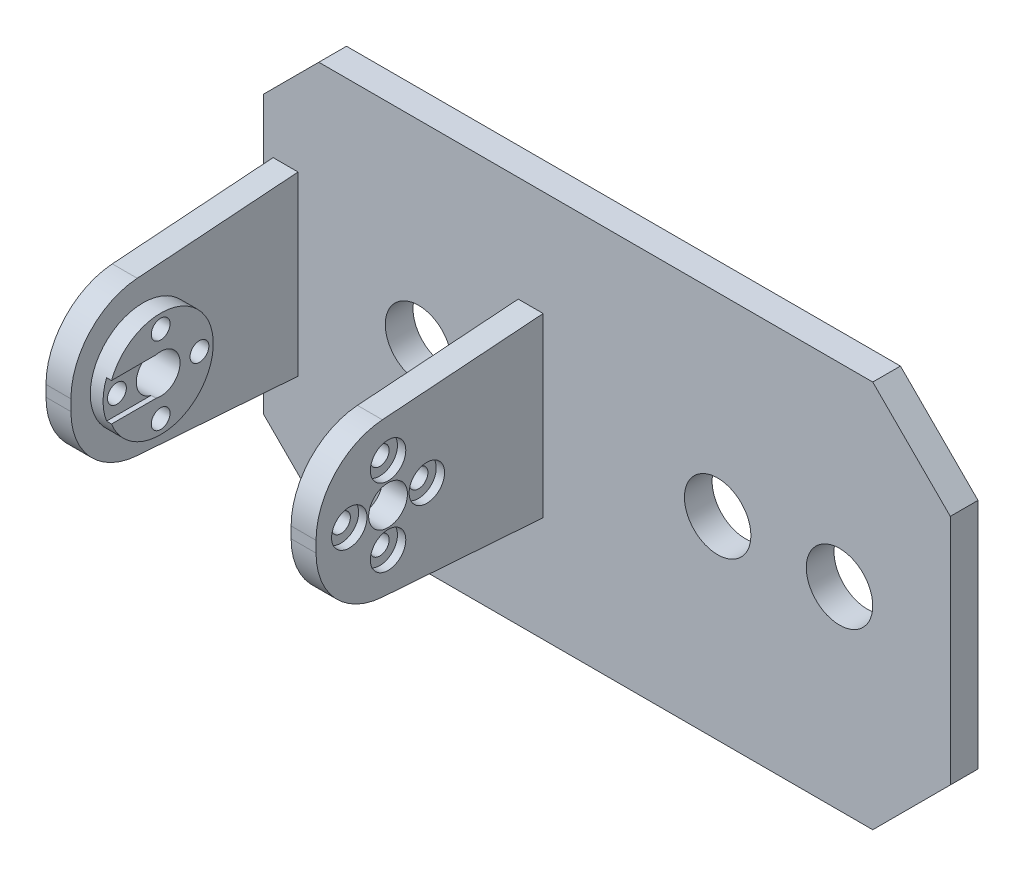
SolidWorks part; units mm, degrees
ref_plane "Front Plane" through (0, 0, 0) normal (0, 0, 1) x (1, 0, 0)
ref_plane "Top Plane" through (0, 0, 0) normal (0, 1, 0) x (1, 0, 0)
ref_plane "Right Plane" through (0, 0, 0) normal (1, 0, 0) x (0, 0, -1)
ref_plane "PZ_m33_000" through (0, 0, -33) normal (0, 0, 1) x (1, 0, 0)
sketch "S_prism1" plane through (0, 0, -33) normal (0, 0, 1) x (1, 0, 0)
  line L0 (56, -21) -> (56, 21)
  line L1 (56, 21) -> (42, 35)
  line L2 (42, 35) -> (-58, 35)
  line L3 (-58, 35) -> (-68, 25)
  line L4 (-68, 25) -> (-68, -25)
  line L5 (-68, -25) -> (-58, -35)
  line L6 (-58, -35) -> (42, -35)
  line L7 (42, -35) -> (56, -21)
extrude "Boss_1" add sketch "S_prism1" along normal blind 5
ref_plane "PX_m22_000" through (-22, 0, 0) normal (1, 0, 0) x (0, 0, -1)
sketch "S_prism2" plane through (-22, 0, 0) normal (1, 0, 0) x (0, 0, -1)
  line L0 (28.5, -16) -> (28.5, 16)
  line L1 (28.5, 16) -> (-1.0301, 13.8653)
  line L2 (-13, 0.9989) -> (-13, -0.9989)
  line L3 (-1.0301, -13.8653) -> (28.5, -16)
  arc A0 (-1.0301, 13.8653) -> (-13, 0.9989) centre (-0.1001, 0.999) ccw
  arc A1 (-13, -0.9989) -> (-1.0301, -13.8653) centre (-0.1001, -0.999) ccw
extrude "Boss_2" add sketch "S_prism2" along normal blind 4.5
ref_plane "PX_m61_750" through (-61.75, 0, 0) normal (1, 0, 0) x (0, 0, -1)
sketch "S_cyl3" plane through (-61.75, 0, 0) normal (1, 0, 0) x (0, 0, -1)
  circle A0 centre (0, 0) radius 9.5
  dimension "D1_S_cyl3" = 19
extrude "Boss_3" add sketch "S_cyl3" along normal blind 3.2
ref_plane "PX_m66_250" through (-66.25, 0, 0) normal (1, 0, 0) x (0, 0, -1)
sketch "S_prism4" plane through (-66.25, 0, 0) normal (1, 0, 0) x (0, 0, -1)
  line L0 (28.5, -16) -> (28.5, 16)
  line L1 (28.5, 16) -> (-1.0301, 13.8653)
  line L2 (-13, 0.9989) -> (-13, -0.9989)
  line L3 (-1.0301, -13.8653) -> (28.5, -16)
  arc A0 (-1.0301, 13.8653) -> (-13, 0.9989) centre (-0.1001, 0.999) ccw
  arc A1 (-13, -0.9989) -> (-1.0301, -13.8653) centre (-0.1001, -0.999) ccw
extrude "Boss_4" add sketch "S_prism4" along normal blind 4.5
ref_plane "PX_m22_100" through (-22.1, 0, 0) normal (1, 0, 0) x (0, 0, -1)
sketch "S_hole5" plane through (-22.1, 0, 0) normal (1, 0, 0) x (0, 0, -1)
  circle A0 centre (0, 0) radius 3.5
  dimension "D1_S_hole5" = 7
extrude "Hole_5" cut sketch "S_hole5" along normal blind 4.7
sketch "S_hole6" plane through (-22.1, 0, 0) normal (1, 0, 0) x (0, 0, -1)
  circle A0 centre (0, 7) radius 1.7
  dimension "D1_S_hole6" = 3.4
  dimension "P2" = 7
extrude "Hole_6" cut sketch "S_hole6" along normal blind 4.7
sketch "S_hole7" plane through (-22.1, 0, 0) normal (1, 0, 0) x (0, 0, -1)
  circle A0 centre (-7, 0) radius 1.7
  dimension "D1_S_hole7" = 3.4
  dimension "P2" = 7
extrude "Hole_7" cut sketch "S_hole7" along normal blind 4.7
sketch "S_hole8" plane through (-22.1, 0, 0) normal (1, 0, 0) x (0, 0, -1)
  circle A0 centre (0, -7) radius 1.7
  dimension "D1_S_hole8" = 3.4
  dimension "P2" = 7
extrude "Hole_8" cut sketch "S_hole8" along normal blind 4.7
sketch "S_hole9" plane through (-22.1, 0, 0) normal (1, 0, 0) x (0, 0, -1)
  circle A0 centre (7, 0) radius 1.7
  dimension "D1_S_hole9" = 3.4
  dimension "P2" = 7
extrude "Hole_9" cut sketch "S_hole9" along normal blind 4.7
ref_plane "PX_m19_000" through (-19, 0, 0) normal (1, 0, 0) x (0, 0, -1)
sketch "S_hole10" plane through (-19, 0, 0) normal (1, 0, 0) x (0, 0, -1)
  circle A0 centre (0, 7) radius 3.2
  dimension "D1_S_hole10" = 6.4
  dimension "P2" = 7
extrude "Hole_10" cut sketch "S_hole10" along normal blind 1.6
sketch "S_hole11" plane through (-19, 0, 0) normal (1, 0, 0) x (0, 0, -1)
  circle A0 centre (-7, 0) radius 3.2
  dimension "D1_S_hole11" = 6.4
  dimension "P2" = 7
extrude "Hole_11" cut sketch "S_hole11" along normal blind 1.6
sketch "S_hole12" plane through (-19, 0, 0) normal (1, 0, 0) x (0, 0, -1)
  circle A0 centre (0, -7) radius 3.2
  dimension "D1_S_hole12" = 6.4
  dimension "P2" = 7
extrude "Hole_12" cut sketch "S_hole12" along normal blind 1.6
sketch "S_hole13" plane through (-19, 0, 0) normal (1, 0, 0) x (0, 0, -1)
  circle A0 centre (7, 0) radius 3.2
  dimension "D1_S_hole13" = 6.4
  dimension "P2" = 7
extrude "Hole_13" cut sketch "S_hole13" along normal blind 1.6
ref_plane "PX_m66_350" through (-66.35, 0, 0) normal (1, 0, 0) x (0, 0, -1)
sketch "S_hole14" plane through (-66.35, 0, 0) normal (1, 0, 0) x (0, 0, -1)
  circle A0 centre (0, 0) radius 3.5
  dimension "D1_S_hole14" = 7
extrude "Hole_14" cut sketch "S_hole14" along normal blind 7.9
sketch "S_hole15" plane through (-66.35, 0, 0) normal (1, 0, 0) x (0, 0, -1)
  circle A0 centre (0, 7) radius 1.7
  dimension "D1_S_hole15" = 3.4
  dimension "P2" = 7
extrude "Hole_15" cut sketch "S_hole15" along normal blind 7.9
sketch "S_hole16" plane through (-66.35, 0, 0) normal (1, 0, 0) x (0, 0, -1)
  circle A0 centre (-7, 0) radius 1.7
  dimension "D1_S_hole16" = 3.4
  dimension "P2" = 7
extrude "Hole_16" cut sketch "S_hole16" along normal blind 7.9
sketch "S_hole17" plane through (-66.35, 0, 0) normal (1, 0, 0) x (0, 0, -1)
  circle A0 centre (0, -7) radius 1.7
  dimension "D1_S_hole17" = 3.4
  dimension "P2" = 7
extrude "Hole_17" cut sketch "S_hole17" along normal blind 7.9
sketch "S_hole18" plane through (-66.35, 0, 0) normal (1, 0, 0) x (0, 0, -1)
  circle A0 centre (7, 0) radius 1.7
  dimension "D1_S_hole18" = 3.4
  dimension "P2" = 7
extrude "Hole_18" cut sketch "S_hole18" along normal blind 7.9
sketch "S_hole19" plane through (-66.35, 0, 0) normal (1, 0, 0) x (0, 0, -1)
  circle A0 centre (0, 7) radius 3.2
  dimension "D1_S_hole19" = 6.4
  dimension "P2" = 7
extrude "Hole_19" cut sketch "S_hole19" along normal blind 2.1
sketch "S_hole20" plane through (-66.35, 0, 0) normal (1, 0, 0) x (0, 0, -1)
  circle A0 centre (-7, 0) radius 3.2
  dimension "D1_S_hole20" = 6.4
  dimension "P2" = 7
extrude "Hole_20" cut sketch "S_hole20" along normal blind 2.1
sketch "S_hole21" plane through (-66.35, 0, 0) normal (1, 0, 0) x (0, 0, -1)
  circle A0 centre (0, -7) radius 3.2
  dimension "D1_S_hole21" = 6.4
  dimension "P2" = 7
extrude "Hole_21" cut sketch "S_hole21" along normal blind 2.1
sketch "S_hole22" plane through (-66.35, 0, 0) normal (1, 0, 0) x (0, 0, -1)
  circle A0 centre (7, 0) radius 3.2
  dimension "D1_S_hole22" = 6.4
  dimension "P2" = 7
extrude "Hole_22" cut sketch "S_hole22" along normal blind 2.1
sketch "S_cut23" plane through (0, 0, 0) normal (0, 0, 1) x (1, 0, 0)
  line L0 (-59.45, -3.4) -> (-58.45, -3.4)
  line L1 (-58.45, -3.4) -> (-58.45, 3.4)
  line L2 (-58.45, 3.4) -> (-59.45, 3.4)
  line L3 (-59.45, 3.4) -> (-59.45, -3.4)
  dimension "P1" = 59.45
  dimension "P2" = 3.4
  dimension "P3" = 58.45
  dimension "P4" = 3.4
  dimension "P5" = 58.45
  dimension "P6" = 3.4
  dimension "P7" = 59.45
  dimension "P8" = 3.4
extrude "Pocket_23" cut sketch "S_cut23" along normal blind 10
ref_plane "PZ_m33_100" through (0, 0, -33.1) normal (0, 0, 1) x (1, 0, 0)
sketch "S_hole24" plane through (0, 0, -33.1) normal (0, 0, 1) x (1, 0, 0)
  circle A0 centre (-40, 0) radius 6
  dimension "D1_S_hole24" = 12
  dimension "P2" = 40
extrude "Hole_24" cut sketch "S_hole24" along normal blind 5.2
sketch "S_hole25" plane through (0, 0, -33.1) normal (0, 0, 1) x (1, 0, 0)
  circle A0 centre (14, 0) radius 6
  dimension "D1_S_hole25" = 12
  dimension "P2" = 14
extrude "Hole_25" cut sketch "S_hole25" along normal blind 5.2
sketch "S_hole26" plane through (0, 0, -33.1) normal (0, 0, 1) x (1, 0, 0)
  circle A0 centre (36, 0) radius 6
  dimension "D1_S_hole26" = 12
  dimension "P2" = 36
extrude "Hole_26" cut sketch "S_hole26" along normal blind 5.2
equation "\"plate_t\" = 3"
equation "\"clearance\" = 0.5"
